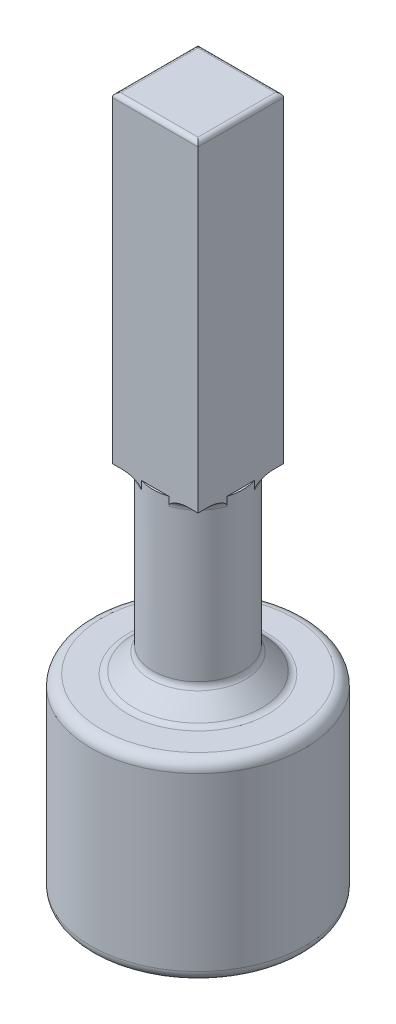
SolidWorks part; units mm, degrees
ref_plane "Front Plane" through (0, 0, 0) normal (0, 0, 1) x (1, 0, 0)
ref_plane "Top Plane" through (0, 0, 0) normal (0, 1, 0) x (1, 0, 0)
ref_plane "Right Plane" through (0, 0, 0) normal (1, 0, 0) x (0, 0, -1)
sketch "Sketch1" plane through (0, 0, 0) normal (0, 1, 0) x (1, 0, 0)
  line L1 (-3.3, 2.55) -> (3.3, 2.55)
  line L2 (-3.3, 2.55) -> (-3.3, -2.55)
  line L3 (-3.3, -2.55) -> (3.3, -2.55)
  line L4 (3.3, 2.55) -> (3.3, -2.55)
  line L5 (-3.3, 2.55) -> (3.3, -2.55) construction
  line L6 (-3.3, -2.55) -> (3.3, 2.55) construction
  circle A1 centre (0, 0) radius 5
  dimension "D2" = 10
  dimension "D1" = 5.1
  dimension "D3" = 6.6
extrude "Boss-Extrude1" add sketch "Sketch1" along normal blind 5
sketch "Sketch2" plane through (0, 5, 0) normal (0, 1, 0) x (1, 0, 0)
  circle A0 centre (0, 0) radius 5
  dimension "D1" = 10
extrude "Boss-Extrude2" add sketch "Sketch2" along normal blind 4
sketch "Sketch3" plane through (0, 9, 0) normal (0, 1, 0) x (1, 0, 0)
  circle A0 centre (0, 0) radius 2.1
  dimension "D1" = 4.2
extrude "Boss-Extrude3" add sketch "Sketch3" along normal blind 8.5
sketch "Sketch4" plane through (0, 17.5, 0) normal (0, 1, 0) x (1, 0, 0)
  line L1 (-2, -2) -> (2, -2)
  line L2 (-2, -2) -> (-2, 2)
  line L3 (-2, 2) -> (2, 2)
  line L4 (2, -2) -> (2, 2)
  line L5 (-2, -2) -> (2, 2) construction
  line L6 (-2, 2) -> (2, -2) construction
  point P0 (0, 0)
  dimension "D1" = 4
extrude "Boss-Extrude4" add sketch "Sketch4" along normal blind 15
chamfer "Chamfer1" distance 1 angle 45 1 edges at (0, 9, 2.1)
fillet "Fillet1" radius 0.4 6 edges at (-1.4849, 17.5, 1.4849) (-1.4849, 17.5, -1.4849) (1.4849, 17.5, -1.4849) (1.4849, 17.5, 1.4849) (0, 10, 2.1) (0, 9, 3.1)
fillet "Fillet2" radius 0.5 2 edges at (0, 0, 5) (0, 9, 5)
fillet "Fillet3" radius 0.2 4 edges at (0, 32.5, -2) (2, 32.5, 0) (0, 32.5, 2) (-2, 32.5, 0)
